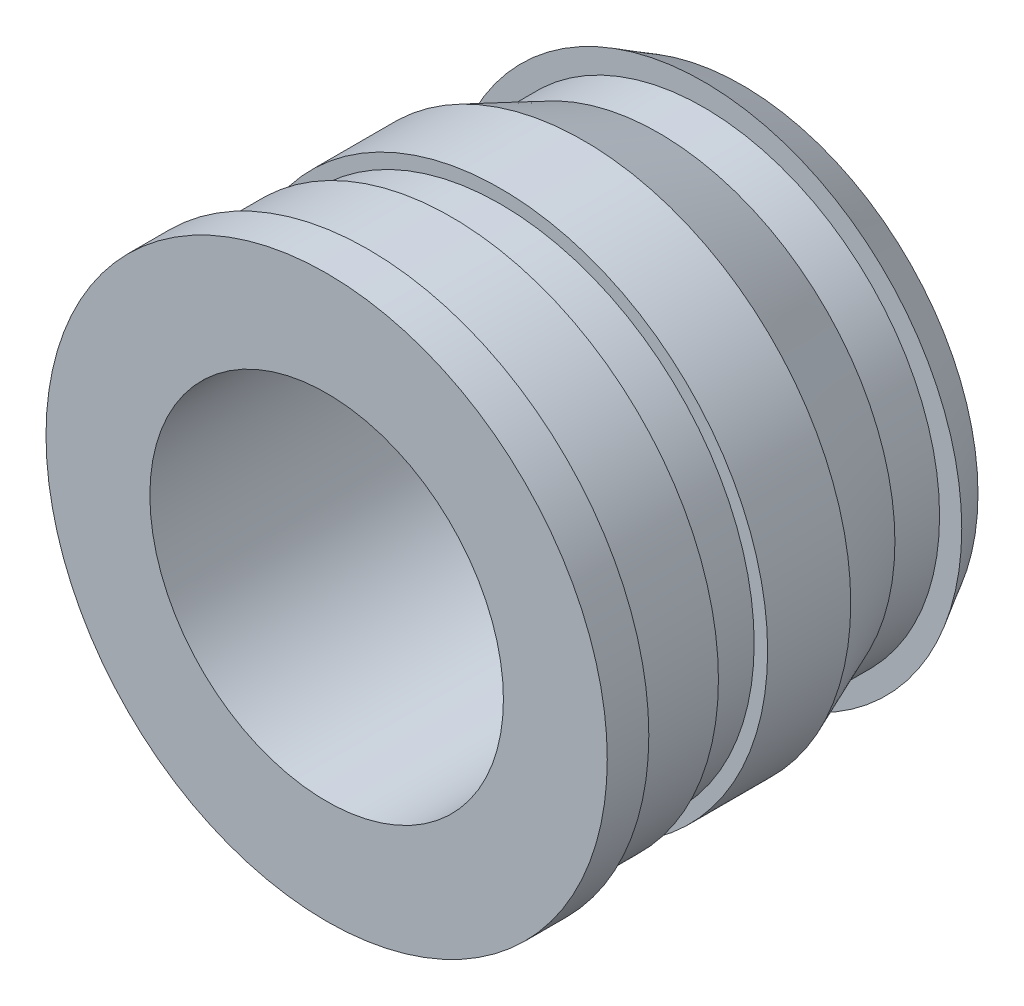
SolidWorks part; units mm, degrees
ref_plane "Front Plane" through (0, 0, 0) normal (0, 0, 1) x (1, 0, 0)
ref_plane "Top Plane" through (0, 0, 0) normal (0, 1, 0) x (1, 0, 0)
ref_plane "Right Plane" through (0, 0, 0) normal (1, 0, 0) x (0, 0, -1)
sketch "Sketch1" plane through (0, 0, 0) normal (1, 0, 0) x (0, 0, -1)
  line L0 (-2.35, 0) -> (2.35, 0) construction
  line L1 (-2.35, 2) -> (-2.35, 3.175)
  line L2 (-2.35, 3.175) -> (-1.88, 3.175)
  line L3 (-1.88, 3.175) -> (-1.88, 3.0225)
  line L4 (-1.88, 3.0225) -> (-0.94, 3.0225)
  line L5 (-0.94, 3.0225) -> (-0.94, 2.87)
  line L6 (-0.94, 2.87) -> (-0.3832, 2.87)
  line L7 (-0.3832, 2.87) -> (-0.3832, 3.0225)
  line L9 (0.5568, 3.0225) -> (1.41, 2.6691)
  line L13 (1.41, 2.6691) -> (1.9154, 2.6691)
  line L14 (1.9154, 2.6691) -> (1.9154, 2.92)
  line L15 (1.9154, 2.92) -> (2.35, 2.6691)
  line L16 (2.35, 2.6691) -> (2.35, 2)
  line L17 (-2.35, 2.92) -> (2.35, 2.92) construction
  line L18 (2.35, 0) -> (2.35, 2.92) construction
  line L19 (-2.35, 0) -> (-2.35, 3.175) construction
  line L20 (-0.3832, 3.0225) -> (0.5568, 3.0225)
  line L21 (-2.35, 2) -> (2.35, 2)
  line L23 (-3.0063, 2.0758) -> (-2.6563, 1.4696) construction
  line L24 (-2.35, -2.92) -> (2.35, -2.92) construction
  line L25 (-2.6563, 1.4696) -> (-2.3063, 2.0758) construction
  line L26 (-2.3063, 2.0758) -> (-3.0063, 2.0758) construction
  line L27 (-2.9625, 2) -> (-2.35, 2) construction
  line L28 (-2.6563, 2.0758) -> (-2.6563, 2) construction
  line L29 (-2.6563, 2) -> (-2.6563, 1.5453) construction
  line L30 (-2.6563, 1.5453) -> (-2.6563, 1.4696) construction
  line L31 (-2.7, 1.5453) -> (-2.6125, 1.5453)
  line L32 (-2.9844, 2.0379) -> (-2.3281, 2.0379)
  line L33 (-2.6125, 1.5453) -> (-2.3281, 2.0379)
  line L34 (-2.7, 1.5453) -> (-2.9844, 2.0379)
  line L35 (-2.35, 2.87) -> (2.35, 2.87) construction
  line L36 (-2.35, -2.87) -> (2.35, -2.87) construction
  point P36 (-2.6563, 2.0379)
  dimension "Installed Length" = 4.7
  dimension "Dia A" = 6.35
  dimension "Dia B" = 5.84
  dimension "Thread Dia" = 4
  dimension "D6" = 30
  dimension "D8" = 0.94
  dimension "D4" = 22.5
  dimension "Thread Pitch" = 0.7
  dimension "D2" = 0.0875
  dimension "Max Hole Dia" = 5.74
  dimension "Knurling Length" = 3.29
  dimension "D1" = 5.3382
  dimension "D3" = 0.47
ref_plane "Plane1" through (0, 0, 1.88) normal (0, 0, 1) x (1, 0, 0)
sketch "Sketch2" plane through (0, 0, 1.88) normal (0, 0, 1) x (1, 0, 0)
  line L0 (0, 0) -> (0, 3.0225) construction
  line L1 (-0.224, 3.0242) -> (0, 2.87)
  line L2 (0.224, 3.0242) -> (0, 2.87)
  line L3 (-0.2108, 3.0151) -> (0, 0) construction
  line L4 (0.2108, 3.0151) -> (0, 0) construction
  line L5 (0, 0) -> (-0.3945, 2.9966) construction
  line L6 (0, 0) -> (0.3945, 2.9966) construction
  line L7 (0, 0) -> (2.1372, 2.1372) construction
  line L8 (0, 0) -> (0, -2.0758) construction
  line L9 (0, 0) -> (1.0379, -1.7977) construction
  circle A0 centre (0, 0) radius 2.87 construction
  circle A1 centre (0, 0) radius 3.0225 construction
  circle A3 centre (0, 0) radius 2.0758
  arc A4 (-0.224, 3.0242) -> (0.224, 3.0242) centre (0, 0) cw
  dimension "Knurl Angle" = 8
  dimension "Pattern Angle" = 15
  dimension "Helix Angle" = 45
  dimension "D1" = 30
sketch "Sketch3" plane through (0, 0, 0) normal (1, 0, 0) x (0, 0, -1)
  line L0 (-2.35, 2) -> (-2.35, 3.175) construction
  line L1 (-2.35, 3.175) -> (-1.88, 3.175) construction
  line L2 (-1.88, 3.175) -> (-1.88, 3.0225) construction
  line L3 (-1.88, 3.0225) -> (-0.94, 3.0225) construction
  line L4 (-0.94, 3.0225) -> (-0.94, 2.87) construction
  line L5 (-0.94, 2.87) -> (-0.3832, 2.87) construction
  line L6 (-0.3832, 2.87) -> (-0.3832, 3.0225) construction
  line L8 (0.5568, 3.0225) -> (1.41, 2.6691) construction
  line L12 (1.41, 2.6691) -> (1.9154, 2.6691) construction
  line L13 (1.9154, 2.6691) -> (1.9154, 2.92) construction
  line L14 (1.9154, 2.92) -> (2.35, 2.6691) construction
  line L15 (2.35, 2.6691) -> (2.35, 2) construction
  line L16 (-2.35, 2) -> (2.35, 2) construction
  line L17 (-2.35, 2) -> (-2.35, 3.175)
  line L18 (-2.35, 3.175) -> (-1.88, 3.175)
  line L19 (-1.88, 3.175) -> (-1.88, 3.0225)
  line L20 (-1.88, 3.0225) -> (-0.94, 3.0225)
  line L21 (-0.94, 3.0225) -> (-0.94, 2.87)
  line L22 (-0.94, 2.87) -> (-0.3832, 2.87)
  line L23 (-0.3832, 2.87) -> (-0.3832, 3.0225)
  line L25 (0.5568, 3.0225) -> (1.41, 2.6691)
  line L29 (1.41, 2.6691) -> (1.9154, 2.6691)
  line L30 (1.9154, 2.6691) -> (1.9154, 2.92)
  line L31 (1.9154, 2.92) -> (2.35, 2.6691)
  line L32 (2.35, 2.6691) -> (2.35, 2)
  line L33 (-2.35, 2) -> (2.35, 2)
  line L34 (-0.3832, 3.0225) -> (0.5568, 3.0225) construction
  line L35 (-0.3832, 3.0225) -> (0.5568, 3.0225)
revolve "Revolve1" add sketch "Sketch3" angle 360 about L0
sketch "Sketch4" [suppressed] plane through (0, 0, 1.88) normal (0, 0, 1) x (1, 0, 0)
  circle A2 centre (0, 0) radius 3.0225 construction
  circle A3 centre (0, 0) radius 3.0225
sketch "Sketch6" [suppressed] plane through (0, 0, 2.35) normal (0, 0, 1) x (1, 0, 0)
  circle A0 centre (0, 0) radius 2
curve "Helix/Spiral2" [suppressed] pitch 0.7 height 5.4 turns 7.7143
sketch "Sketch7" [suppressed] plane through (0, 0, 0) normal (1, 0, 0) x (0, 0, -1)
  line L0 (-2.7, 1.5453) -> (-2.6125, 1.5453) construction
  line L1 (-2.7, 1.5453) -> (-2.9844, 2.0379) construction
  line L2 (-2.9844, 2.0379) -> (-2.3281, 2.0379) construction
  line L3 (-2.6125, 1.5453) -> (-2.3281, 2.0379) construction
  line L4 (-2.7, 1.5453) -> (-2.6125, 1.5453)
  line L5 (-2.7, 1.5453) -> (-2.9844, 2.0379)
  line L6 (-2.9844, 2.0379) -> (-2.3281, 2.0379)
  line L7 (-2.6125, 1.5453) -> (-2.3281, 2.0379)
sweep "Sweep1" [suppressed] add profiles "Sketch7" path "Helix/Spiral2"
sketch "Sketch8" [suppressed] plane through (0, 0, 2.35) normal (0, 0, 1) x (1, 0, 0)
  circle A0 centre (0, 0) radius 2.0758
extrude "Cut-Extrude1" [suppressed] cut sketch "Sketch8" against normal through all draft 45 and the other way through all
mirror "Mirror1" [suppressed] about plane through (0, 0, 0) normal (0, 0, 1)
curve "Helix/Spiral1" [suppressed] pitch 26.32 height 3.29 turns 0.125
sketch "Sketch5" [suppressed] plane through (0, 0, 1.88) normal (0, 0, 1) x (1, 0, 0)
  line L0 (-0.224, 3.0242) -> (0, 2.87) construction
  line L1 (0.224, 3.0242) -> (0, 2.87) construction
  line L2 (-0.224, 3.0242) -> (0, 2.87)
  line L3 (0.224, 3.0242) -> (0, 2.87)
  arc A2 (0.224, 3.0242) -> (-0.224, 3.0242) centre (0, 0) ccw construction
  arc A3 (0.224, 3.0242) -> (-0.224, 3.0242) centre (0, 0) ccw
sweep "Cut-Sweep1" [suppressed] cut profiles "Sketch5" path "Helix/Spiral1"
pattern_circular "CirPattern1" [suppressed] count 24 over 360 about axis through (0, 0, 2.35) along (0, 0, -1) of bodies 105
equation "\"D8@Sketch1\"=\"Installed Length@Sketch1\" * .2"
equation "\"D4@Helix/Spiral1\"=\"Knurling Length@Sketch1\"*(360/\"Helix Angle@Sketch2\")"
equation "\"D3@Helix/Spiral1\"=\"Knurling Length@Sketch1\""
equation "\"D1@CirPattern1\"=\"D3@CirPattern1\"/\"Pattern Angle@Sketch2\""
equation "\"D2@Sketch1\" = \"Thread Pitch@Sketch1\" / 8"
equation "\"D4@Helix/Spiral2\"=\"Thread Pitch@Sketch1\""
equation "\"D3@Helix/Spiral2\" = \"Installed Length@Sketch1\" + \"Thread Pitch@Sketch1\""
equation "\"Knurling Length@Sketch1\"=\"Installed Length@Sketch1\" * .7"
equation "\"D1@Sketch1\"=\"Max Hole Dia@Sketch1\"*.93"
equation "\"D3@Sketch1\"=\"Installed Length@Sketch1\"*.1"
